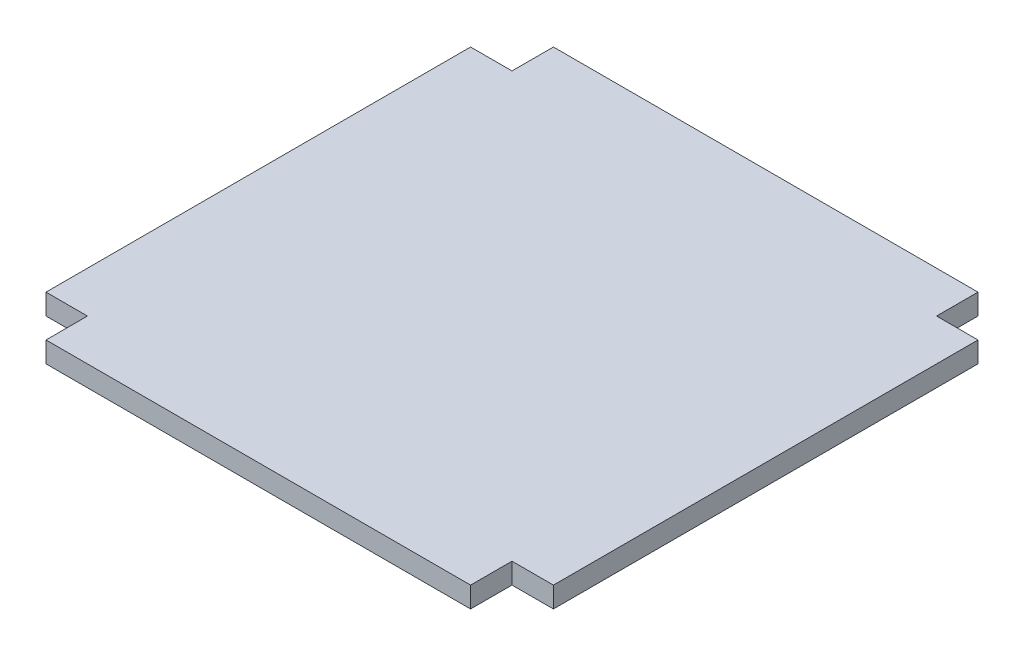
SolidWorks part; units mm, degrees
ref_plane "Front Plane" through (0, 0, 0) normal (0, 0, 1) x (1, 0, 0)
ref_plane "Top Plane" through (0, 0, 0) normal (0, 1, 0) x (1, 0, 0)
ref_plane "Right Plane" through (0, 0, 0) normal (1, 0, 0) x (0, 0, -1)
sketch "Sketch1" plane through (0, 0, 0) normal (0, 1, 0) x (1, 0, 0)
  line L1 (-245, -245) -> (245, -245)
  line L2 (-245, -245) -> (-245, 245)
  line L3 (-245, 245) -> (245, 245)
  line L4 (245, -245) -> (245, 245)
  line L5 (-245, -245) -> (245, 245) construction
  line L6 (-245, 245) -> (245, -245) construction
  point P0 (0, 0)
  dimension "D1" = 490
  dimension "D2" = 490
extrude "Boss-Extrude1" add sketch "Sketch1" along normal blind 20
sketch "Sketch2" plane through (0, 20, 0) normal (0, 1, 0) x (1, 0, 0)
  line L1 (-245, 245) -> (-205, 245)
  line L2 (-245, 245) -> (-245, 205)
  line L3 (-245, 205) -> (-205, 205)
  line L4 (-205, 245) -> (-205, 205)
  dimension "D1" = 40
  dimension "D2" = 40
extrude "Cut-Extrude1" cut sketch "Sketch2" against normal through all
sketch "Sketch3" plane through (0, 20, 0) normal (0, 1, 0) x (1, 0, 0)
  line L1 (245, 245) -> (205, 245)
  line L2 (245, 245) -> (245, 205)
  line L3 (245, 205) -> (205, 205)
  line L4 (205, 245) -> (205, 205)
  line L5 (-245, -245) -> (-205, -245)
  line L6 (-245, -245) -> (-245, -205)
  line L7 (-245, -205) -> (-205, -205)
  line L8 (-205, -245) -> (-205, -205)
  line L9 (245, -245) -> (205, -245)
  line L10 (245, -245) -> (245, -205)
  line L11 (245, -205) -> (205, -205)
  line L12 (205, -245) -> (205, -205)
  dimension "D1" = 40
  dimension "D2" = 40
  dimension "D3" = 40
  dimension "D4" = 40
  dimension "D5" = 40
  dimension "D6" = 40
extrude "Cut-Extrude3" cut sketch "Sketch3" against normal through all
